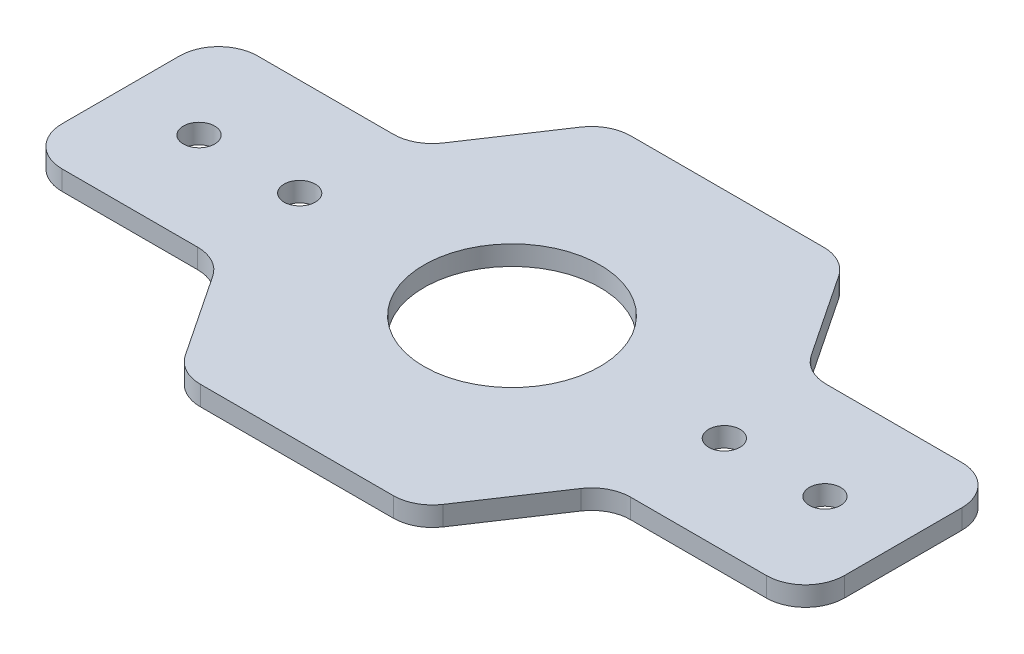
SolidWorks part; units mm, degrees
ref_plane "Front Plane" through (0, 0, 0) normal (0, 0, 1) x (1, 0, 0)
ref_plane "Top Plane" through (0, 0, 0) normal (0, 1, 0) x (1, 0, 0)
ref_plane "Right Plane" through (0, 0, 0) normal (1, 0, 0) x (0, 0, -1)
sketch "Sketch1" plane through (0, 0, 0) normal (0, 1, 0) x (1, 0, 0)
  line L0 (16.2686, 0) -> (85.3314, 0) construction
  line L1 (50.8, 0) -> (50.8, 3.1391) construction
  line L2 (19.05, 15.875) -> (31.75, 34.925)
  line L3 (-12.7, 15.875) -> (19.05, 15.875)
  line L4 (-12.7, 15.875) -> (-12.7, -15.875)
  line L5 (-12.7, -15.875) -> (19.05, -15.875)
  line L6 (114.3, 15.875) -> (114.3, -15.875)
  line L7 (-12.7, 15.875) -> (114.3, -15.875) construction
  line L8 (-12.7, -15.875) -> (114.3, 15.875) construction
  line L9 (31.75, 34.925) -> (69.85, 34.925)
  line L10 (69.85, 34.925) -> (82.55, 15.875)
  line L11 (50.8, 34.925) -> (50.8, 29.0511) construction
  line L12 (69.85, -34.925) -> (82.55, -15.875)
  line L13 (31.75, -34.925) -> (69.85, -34.925)
  line L14 (19.05, -15.875) -> (31.75, -34.925)
  line L15 (82.55, -15.875) -> (114.3, -15.875)
  line L16 (82.55, 15.875) -> (114.3, 15.875)
  circle A0 centre (0, 0) radius 2.54
  circle A1 centre (101.6, 0) radius 2.54
  circle A2 centre (16.2686, 0) radius 2.54 construction
  circle A3 centre (85.3314, 0) radius 2.54 construction
  dimension "D1" = 5.08
  dimension "D3" = 127
  dimension "D4" = 31.75
  dimension "D5" = 69.0628
  dimension "D2" = 101.6
  dimension "D6" = 19.05
  dimension "D7" = 31.75
  dimension "D8" = 38.1
extrude "Boss-Extrude1" add sketch "Sketch1" along normal blind 3.175
fillet "Fillet1" radius 6.35 12 edges at (19.05, 1.5875, -15.875) (31.75, 1.5875, -34.925) (69.85, 1.5875, -34.925) (82.55, 1.5875, -15.875) (114.3, 1.5875, -15.875) (114.3, 1.5875, 15.875) (82.55, 1.5875, 15.875) (69.85, 1.5875, 34.925) (31.75, 1.5875, 34.925) (19.05, 1.5875, 15.875) (-12.7, 1.5875, -15.875) (-12.7, 1.5875, 15.875)
sketch "Sketch2" plane through (0, 3.175, 0) normal (0, 1, 0) x (1, 0, 0)
  circle A0 centre (50.8, 0) radius 14.2875
  circle A1 centre (0, 0) radius 2.54 construction
  dimension "D1" = 50.8
  dimension "D2" = 28.575
extrude "Cut-Extrude1" cut sketch "Sketch2" against normal blind 3.175
sketch "Sketch3" plane through (0, 3.175, 0) normal (0, 1, 0) x (1, 0, 0)
  line L0 (50.8, 0) -> (50.8, -34.925) construction
  line L1 (35.1484, -34.925) -> (66.4516, -34.925) construction
  circle A2 centre (85.2619, 0) radius 2.54
  circle A3 centre (16.3381, 0) radius 2.54
  point P10 (0, 0)
  dimension "D1" = 68.9238
  dimension "D2" = 5.08
  dimension "D3" = 5.08
extrude "Cut-Extrude2" cut sketch "Sketch3" against normal through all
